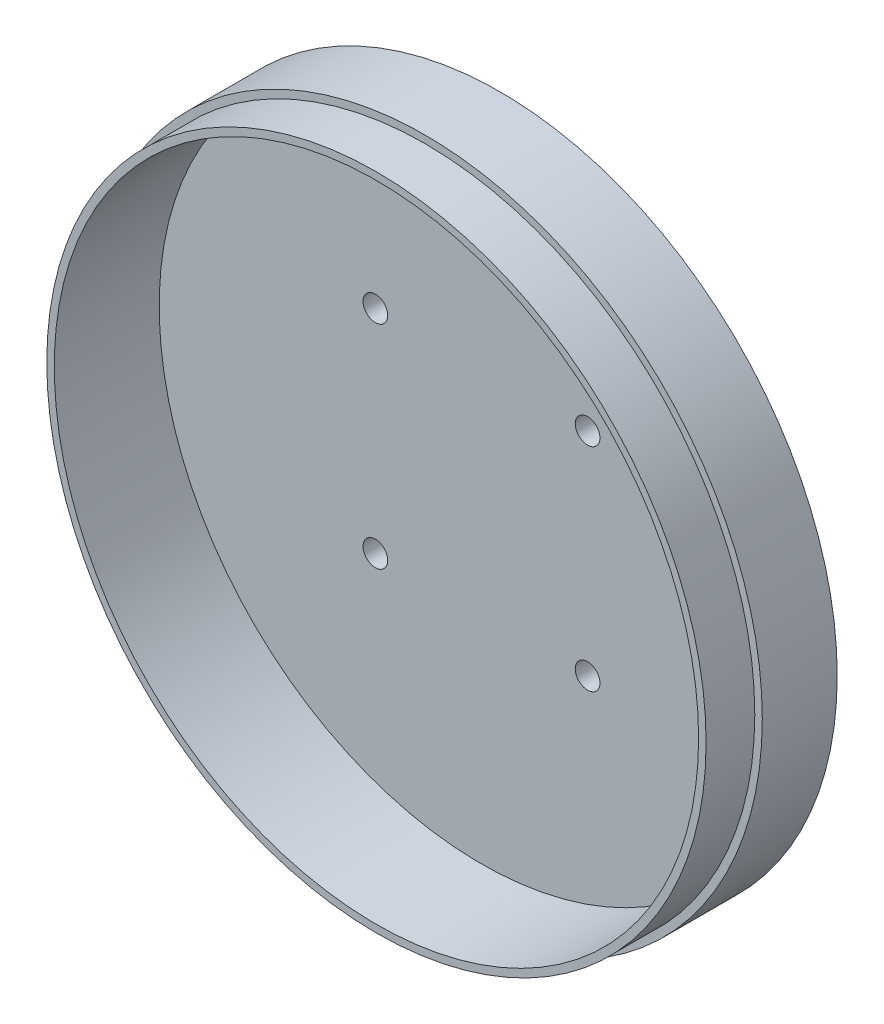
SolidWorks part; units mm, degrees
note: The reader was unsure of these and kept them because the rebuilt part matched: shared geometry of "Sketch1<4>".
ref_plane "Front Plane" through (0, 0, 0) normal (0, 0, 1) x (1, 0, 0)
ref_plane "Top Plane" through (0, 0, 0) normal (0, 1, 0) x (1, 0, 0)
ref_plane "Right Plane" through (0, 0, 0) normal (1, 0, 0) x (0, 0, -1)
sketch "Sketch1" plane through (0, 0, 0) normal (0, 0, 1) x (1, 0, 0)
  circle A0 centre (0, 0) radius 44
  circle A1 centre (0, 0) radius 43
  dimension "D1" = 88
  dimension "D2" = 86
extrude "Boss-Extrude1" add sketch "Sketch1" along normal blind 14
extrude "Boss-Extrude2" add sketch "Sketch1<4>" against normal blind 2.5 separate body contours A1 | A0 A1
sketch "Sketch1<4>" plane through (0, 0, 0) normal (0, 0, 1) x (1, 0, 0) same geometry as "Sketch1"
sketch "Sketch3" plane through (0, 0, -2.5) normal (0, 0, -1) x (-1, 0, 0)
  line L0 (0, 0) -> (20, 0) construction
  line L1 (0, 0) -> (14.1421, 14.1421) construction
  circle A0 centre (0, 0) radius 20 construction
  dimension "D1" = 40
  dimension "D2" = 45
hole_wizard "M4x0.7 Tapped Hole1" positions "Sketch4" profile "Sketch5" tap size "M4x0.7" standard "ANSI Metric" end condition through all
sketch "Sketch4" plane through (0, 0, -2.5) normal (0, 0, -1) x (-1, 0, 0)
  point P0 (14.1421, 14.1421)
sketch "Sketch5" plane through (-14.1421, 14.1421, -2.5) normal (1, 0, 0) x (0, 1, 0)
  line L0 (0, 0) -> (0, 2.5)
  line L1 (0, 2.5) -> (1.65, 2.5)
  line L2 (1.65, 2.5) -> (1.65, 0)
  line L5 (1.65, 0) -> (0, 0)
  line L11 (0, -6.35) -> (0, 107.95) construction
  dimension "Thru Tap Drill Dia." = 3.3
  dimension "Thru Tap Drill Depth" = 2.5
cosmetic thread "Hole Thread1" parameters "D2"=4
pattern_circular "CirPattern1" count 4 over 360 about axis through (0.0199, -0.0199, 0) along (0, 0, 1) of "M4x0.7 Tapped Hole1"
cosmetic thread "Hole Thread2" parameters "D2"=4
cosmetic thread "Hole Thread3" parameters "D2"=4
cosmetic thread "Hole Thread4" parameters "D2"=4
sketch "Sketch6" plane through (0, 0, -2.5) normal (0, 0, -1) x (-1, 0, 0)
  circle A0 centre (0, 0) radius 45
  circle A1 centre (0, 0) radius 44 construction
  circle A2 centre (0, 0) radius 44
  dimension "D1" = 90
extrude "Boss-Extrude3" add sketch "Sketch6" against normal blind 10
